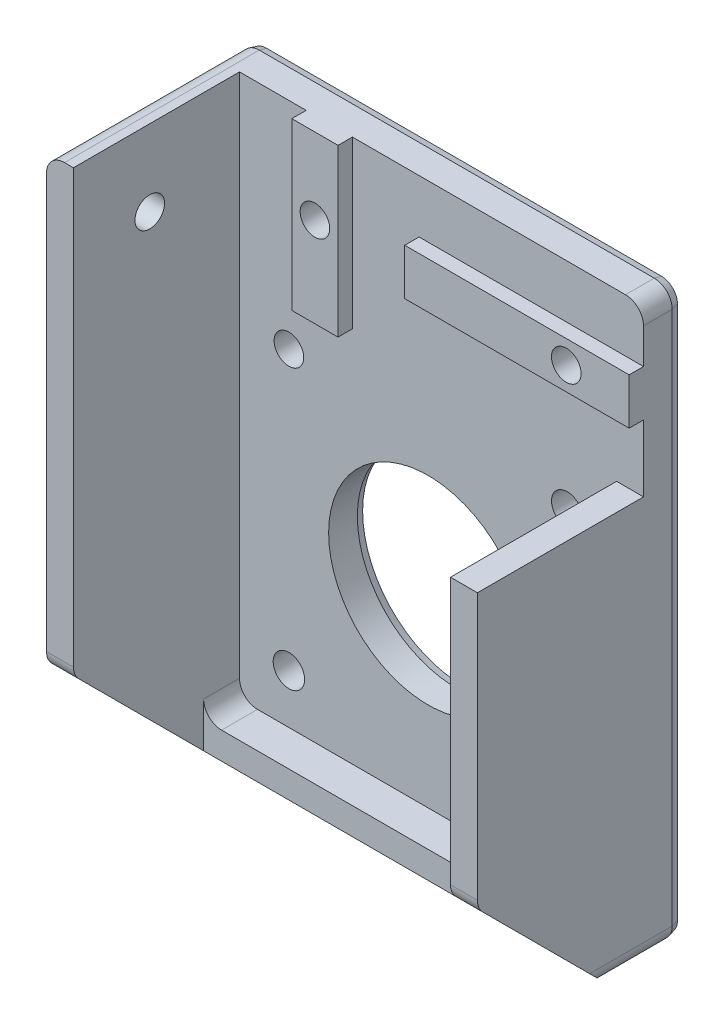
SolidWorks part; units mm, degrees
ref_plane "Спереди" through (0, 0, 0) normal (0, 0, 1) x (1, 0, 0)
ref_plane "Сверху" through (0, 0, 0) normal (0, 1, 0) x (1, 0, 0)
ref_plane "Справа" through (0, 0, 0) normal (1, 0, 0) x (0, 0, -1)
sketch "Sketch1" plane through (0, 0, 0) normal (0, 0, 1) x (1, 0, 0)
  line L0 (-24, -24) -> (24, -24)
  line L1 (-24, -24) -> (-24, 39.5)
  line L2 (-24, 39.5) -> (24, 39.5)
  line L3 (24, -24) -> (24, 39.5)
  line L4 (-21, 39.5) -> (-21, -24)
  line L5 (21, 39.5) -> (21, -24)
  line L6 (-21, -21) -> (21, -21)
  line L7 (24, 21) -> (21, 21)
  line L8 (-11, 14.0121) -> (-11, 30.523) construction
  line L9 (-0.8377, 31) -> (17, 31) construction
  circle A0 centre (-11, 31) radius 1.65
  circle A1 centre (17, 31) radius 1.65
  circle A2 centre (0, 0) radius 11.075
  circle A3 centre (-15.5, 15.5) radius 1.65
  circle A4 centre (15.5, 15.5) radius 1.75
  circle A5 centre (15.5, -15.5) radius 1.75
  circle A6 centre (-15.5, -15.5) radius 1.75
  point P29 (0.1623, -7.0274)
  dimension "D4" = 3.3
  dimension "D6" = 3.3
  dimension "D7" = 22.15
  dimension "D1" = 3
  dimension "D2" = 3
  dimension "D3" = 3
  dimension "D5" = 7
  dimension "D8" = 39.5
  dimension "D9" = 48
  dimension "D10" = 24
  dimension "D11" = 8.5
  dimension "D12" = 24
  dimension "D13" = 31
  dimension "D14" = 31
  dimension "D15" = 31
  dimension "D16" = 31
  dimension "D17" = 8.5
  dimension "D18" = 8.5
  dimension "D19" = 13
  dimension "D20" = 63.5
  dimension "D21" = 18.5
extrude "Extrude1" add sketch "Sketch1" along normal blind 4 contours L4 L6 L5 L2 A6 A5 A4 A3 A2 A1 A0 | L7 L3 L2 L5 region at (-20.2635, 9.25, 0) region at (22.5, 30.25, 0)
extrude "Extrude2" add sketch "Sketch" along normal blind 22.5 contours L4 L2 L1 L0 | L3 L7 L5 L0 region at (-22.5, 7.75, 0) region at (22.5, -1.5, 0)
sketch "Sketch" plane through (0, 0, 0) normal (0, 0, 1) x (1, 0, 0) same geometry as "Sketch1"
extrude "Extrude3" add sketch "Sketch" along normal blind 8 contours L6 L4 L0 L5 region at (0, -22.5, 0)
sketch "Sketch" plane through (0, 0, 0) normal (0, 0, 1) x (1, 0, 0) same geometry as "Sketch1"
sketch "Sketch2" plane through (-21, 0, 0) normal (1, 0, 0) x (0, 0, -1)
  line L0 (-8, -24) -> (-22.5, -9.5)
  line L1 (-22.5, 39.5) -> (-22.5, -24) construction
  line L2 (-22.5, -9.5) -> (-22.5, -24)
  line L3 (-22.5, -24) -> (-8, -24)
  dimension "D1" = 45
extrude "Extrude4" cut sketch "Sketch2" against normal up to next and the other way up to next
fillet "Fillet1" radius 2 8 edges at (22.5, -9.5, 22.5) (-22.5, -9.5, 22.5) (24, -24, 4) (-24, -24, 4) (-24, 39.5, 11.25) (24, 39.5, 2) (21, -21, 6) (-21, -21, 6)
sketch "Sketch3" plane through (-21, 0, 0) normal (1, 0, 0) x (0, 0, -1)
  line L1 (-4, 39.5) -> (-4, -19) construction
  line L2 (-22.5, 39.5) -> (-4, 39.5) construction
  circle A0 centre (-14, 31) radius 1.65
  dimension "D1" = 3.3
  dimension "D2" = 10
  dimension "D3" = 8.5
extrude "Extrude5" cut sketch "Sketch3" against normal up to next
sketch "Sketch4" plane through (0, 0, 4) normal (0, 0, 1) x (1, 0, 0)
  line L0 (-11, 41.6035) -> (-11, 20.5382) construction
  line L1 (17, 31) -> (-0.7543, 31) construction
  line L2 (-21, 39.5) -> (22, 39.5) construction
  line L3 (-13.575, 21) -> (-8.425, 21)
  line L4 (-13.575, 21) -> (-13.575, 27.8)
  line L5 (-13.575, 27.8) -> (-8.425, 27.8)
  line L6 (-8.425, 21) -> (-8.425, 27.8)
  line L7 (-13.575, 21) -> (-8.425, 27.8) construction
  line L8 (-13.575, 27.8) -> (-8.425, 21) construction
  line L9 (-13.575, 34.2) -> (-8.425, 34.2)
  line L10 (-13.575, 34.2) -> (-13.575, 39.5)
  line L11 (-13.575, 39.5) -> (-8.425, 39.5)
  line L12 (-8.425, 34.2) -> (-8.425, 39.5)
  line L13 (-13.575, 34.2) -> (-8.425, 39.5) construction
  line L14 (-13.575, 39.5) -> (-8.425, 34.2) construction
  line L15 (-21, 39.5) -> (-21, -19) construction
  line L16 (-1, 33.575) -> (13.8, 33.575)
  line L17 (-1, 33.575) -> (-1, 28.425)
  line L18 (-1, 28.425) -> (13.8, 28.425)
  line L19 (13.8, 33.575) -> (13.8, 28.425)
  line L20 (-1, 33.575) -> (13.8, 28.425) construction
  line L21 (-1, 28.425) -> (13.8, 33.575) construction
  line L22 (24, 21) -> (21, 21) construction
  line L23 (-13.575, 27.8) -> (-13.575, 34.2)
  line L24 (-8.425, 27.8) -> (-8.425, 34.2)
  line L25 (13.8, 33.575) -> (24, 33.575)
  line L26 (24, 21) -> (24, 37.5) construction
  line L27 (24, 33.575) -> (24, 28.425)
  line L28 (24, 28.425) -> (13.8, 28.425)
  circle A0 centre (-11, 31) radius 1.65 construction
  point P6 (-11, 24.4)
  point P11 (-11, 36.85)
  point P18 (6.4, 31)
  circle M6 centre (17, 31) radius 1.65
  circle M7 centre (-11, 31) radius 1.65
  line M8 (24, 21) -> (24, 37.5)
  line M10 (22, 39.5) -> (-21, 39.5)
  dimension "D5" = 3.2
  dimension "D1" = 5.15
  dimension "D3" = 5.15
  dimension "D4" = 3.2
  dimension "D6" = 3.2
  dimension "D7" = 20
extrude "Extrude6" [suppressed] add sketch "Sketch4" along normal blind 5 contours L3 L6 L5 L4 | L9 L12 L10 M10 | L19 L16 L17 L18
extrude "Extrude7" add sketch "Sketch" along normal blind 1.6 contours L5 L24 L9 L23 M7 | L28 L25 L19 M8 M6 | L9 L12 L10 M10 | L3 L6 L5 L4 | L19 L16 L17 L18 region at (-11, 24.4, 4) region at (-13.4929, 31, 4) region at (-11, 36.85, 4) region at (6.4, 31, 4) region at (19.2695, 31, 4)
sketch "Sketch" plane through (0, 0, 4) normal (0, 0, 1) x (1, 0, 0) same geometry as "Sketch4"
chamfer "Chamfer1" distance 0.8 angle 15 15 edges at (17.25, -15.5, 0) (11.075, 0, 0) (-13.75, -15.5, 0) (-13.85, 15.5, 0) (-9.35, 31, 0) (17.25, 15.5, 0) (18.65, 31, 0) (-23.4142, -23.4142, 0) (-24, 7.75, 0) (0, -24, 0) (-23.4142, 38.9142, 0) (23.4142, -23.4142, 0) (0, 39.5, 0) (24, 7.75, 0) (23.4142, 38.9142, 0) first distance on face at (17.25, -15.5, 4) first distance on face at (11.075, 0, 4) first distance on face at (-13.75, -15.5, 4) first distance on face at (-13.85, 15.5, 4) first distance on face at (-9.35, 31, 0) first distance on face at (17.25, 15.5, 4) first distance on face at (18.65, 31, 0) first distance on face at (-23.2071, -23.2071, 4.3964) first distance on face at (-24, 29.35, 14) first distance on face at (0, -24, 5.3333) first distance on face at (-23.2071, 38.7071, 11.25) first distance on face at (23.2071, -23.2071, 4.3964) first distance on face at (-10.4925, 39.5, 8.145) first distance on face at (24, 14.8487, 8.6879) first distance on face at (23.2071, 38.7071, 2)
